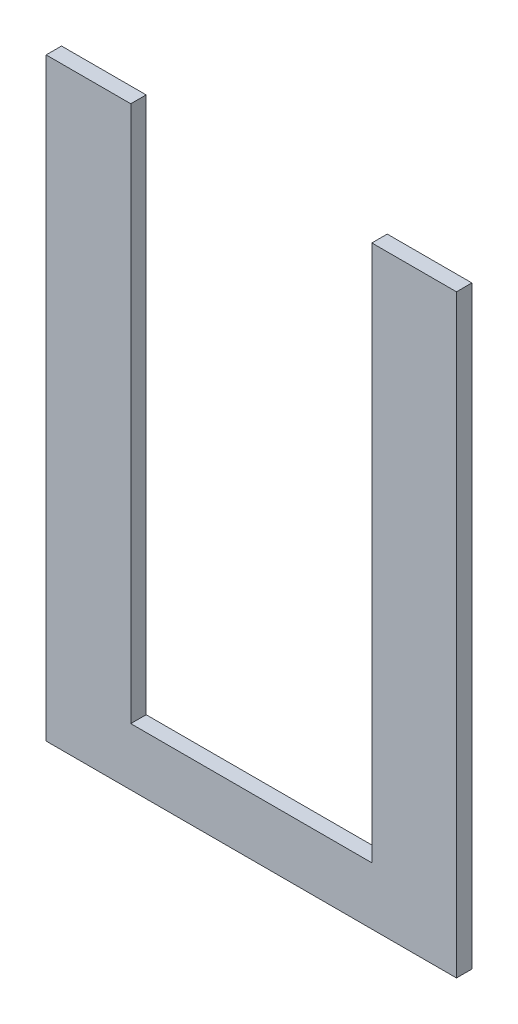
SolidWorks part; units mm, degrees
ref_plane "Front Plane" through (0, 0, 0) normal (0, 0, 1) x (1, 0, 0)
ref_plane "Top Plane" through (0, 0, 0) normal (0, 1, 0) x (1, 0, 0)
ref_plane "Right Plane" through (0, 0, 0) normal (1, 0, 0) x (0, 0, -1)
sketch "Sketch1" plane through (0, 0, 0) normal (0, 0, 1) x (1, 0, 0)
  line L0 (16.5, 115.857) -> (16.5, 11.2)
  line L1 (0, 0) -> (80, 0)
  line L2 (0, 0) -> (0, 115.857)
  line L3 (0, 115.857) -> (80, 115.857) construction
  line L4 (80, 0) -> (80, 115.857)
  line L5 (16.5, 11.2) -> (63.5, 11.2)
  line L6 (63.5, 11.2) -> (63.5, 115.857)
  line L7 (63.5, 115.857) -> (80, 115.857)
  line L8 (16.5, 115.857) -> (0, 115.857)
  line L9 (40, 115.857) -> (40, 0) construction
sketch "Sketch2" plane through (0, 0, 0) normal (0, 1, 0) x (1, 0, 0)
  line L1 (0, 0) -> (80, 0)
  line L2 (0, 0) -> (0, 3)
  line L3 (0, 3) -> (80, 3)
  line L4 (80, 0) -> (80, 3)
extrude "Boss-Extrude1" add sketch "Sketch1" against normal up to vertex (3 mm away) up to point (0, 0, -3)
